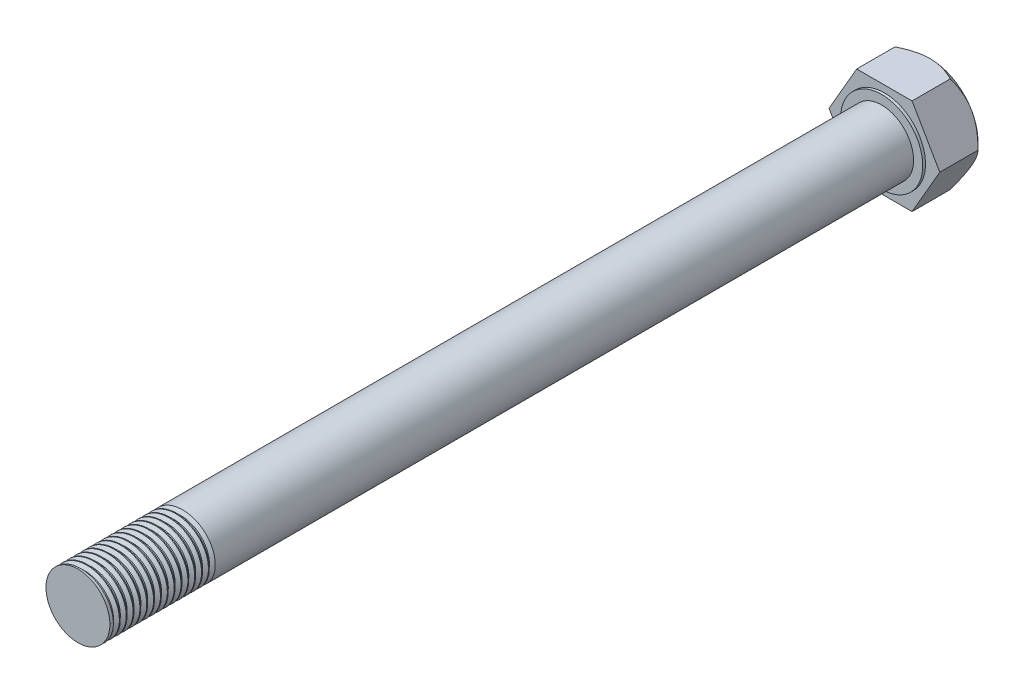
SolidWorks part; units mm, degrees
ref_plane "Front Plane" through (0, 0, 0) normal (0, 0, 1) x (1, 0, 0)
ref_plane "Top Plane" through (0, 0, 0) normal (0, 1, 0) x (1, 0, 0)
ref_plane "Right Plane" through (0, 0, 0) normal (1, 0, 0) x (0, 0, -1)
sketch "Sketch1" plane through (0, 0, 0) normal (0, 0, 1) x (1, 0, 0)
  circle A0 centre (0, 0) radius 7
  dimension "D1" = 14
extrude "Boss-Extrude1" add sketch "Sketch1" along normal blind 99 and the other way blind 77
ref_plane "Plane1" [suppressed] through (0, 0, -88) normal (0, 0, -1) x (-1, 0, 0)
sketch "Sketch2" [suppressed] plane through (0, 0, -88) normal (0, 0, -1) x (-1, 0, 0)
  line L1 (-7.5, 7.5) -> (7.5, 7.5)
  line L2 (-7.5, 7.5) -> (-7.5, -7.5)
  line L3 (-7.5, -7.5) -> (7.5, -7.5)
  line L4 (7.5, 7.5) -> (7.5, -7.5)
  line L5 (-7.5, 7.5) -> (7.5, -7.5) construction
  line L6 (-7.5, -7.5) -> (7.5, 7.5) construction
  point P0 (0, 0)
  dimension "D1" = 15
thread "Thread1" pitch 1.5 method cut profile "Thread Profile1" start angle 0, offset 0, length 22, pitch 1.5, diameter 14
ref_plane "Plane2" through (-7, 0, 99) normal (0, -1, 0) x (-1, 0, 0)
sketch "Thread Profile1" plane through (-7, 0, 99) normal (0, -1, 0) x (-1, 0, 0)
  line L0 (0, 0) -> (0, 1.5) construction
  line L11 (0, 0) -> (0, 1.3125)
  line L12 (0, 1.3125) -> (-0.8119, 0.8437)
  line L13 (-0.8119, 0.8437) -> (-0.8119, 0.4687)
  line L15 (-0.8119, 0.4687) -> (0, 0)
  line L17 (-0.8119, 0.6562) -> (0, 0.6562) construction
  point P2 (0, 0)
  dimension "Pitch" = 1.5
  dimension "Profile_Angle" = 60
  dimension "Profile_Land" = 0.375
  dimension "Profile_Height" = 0.8119
sketch "Sketch3" [suppressed] plane through (0, 0, -83) normal (0, 0, -1) x (-1, 0, 0)
  line L1 (12.1244, 0) -> (6.0622, 10.5)
  line L2 (6.0622, 10.5) -> (-6.0622, 10.5)
  line L3 (-6.0622, 10.5) -> (-12.1244, 0)
  line L4 (-12.1244, 0) -> (-6.0622, -10.5)
  line L5 (-6.0622, -10.5) -> (6.0622, -10.5)
  line L6 (6.0622, -10.5) -> (12.1244, 0)
  circle A1 centre (0, 0) radius 10.5 construction
  dimension "D1" = 21
extrude "Boss-Extrude3" [suppressed] add sketch "Sketch3" along normal blind 10
sketch "Sketch4" plane through (0, 0, -77) normal (0, 0, -1) x (-1, 0, 0)
  circle A0 centre (0, 0) radius 9
  dimension "D1" = 18
extrude "Boss-Extrude4" add sketch "Sketch4" along normal blind 0.6
sketch "Sketch5" plane through (0, 0, -77.6) normal (0, 0, -1) x (-1, 0, 0)
  line L1 (12.1244, 0) -> (6.0622, 10.5)
  line L2 (6.0622, 10.5) -> (-6.0622, 10.5)
  line L3 (-6.0622, 10.5) -> (-12.1244, 0)
  line L4 (-12.1244, 0) -> (-6.0622, -10.5)
  line L5 (-6.0622, -10.5) -> (6.0622, -10.5)
  line L6 (6.0622, -10.5) -> (12.1244, 0)
  circle A0 centre (0, 0) radius 10.5 construction
  dimension "D1" = 21
extrude "Boss-Extrude5" add sketch "Sketch5" along normal blind 10
sketch "Sketch6" plane through (0, 0, -87.6) normal (0, 0, -1) x (-1, 0, 0)
  circle A0 centre (0, 0) radius 10.5
  dimension "D1" = 21
extrude "Cut-Extrude1" cut sketch "Sketch6" against normal blind 10 draft 45 flip side to cut
